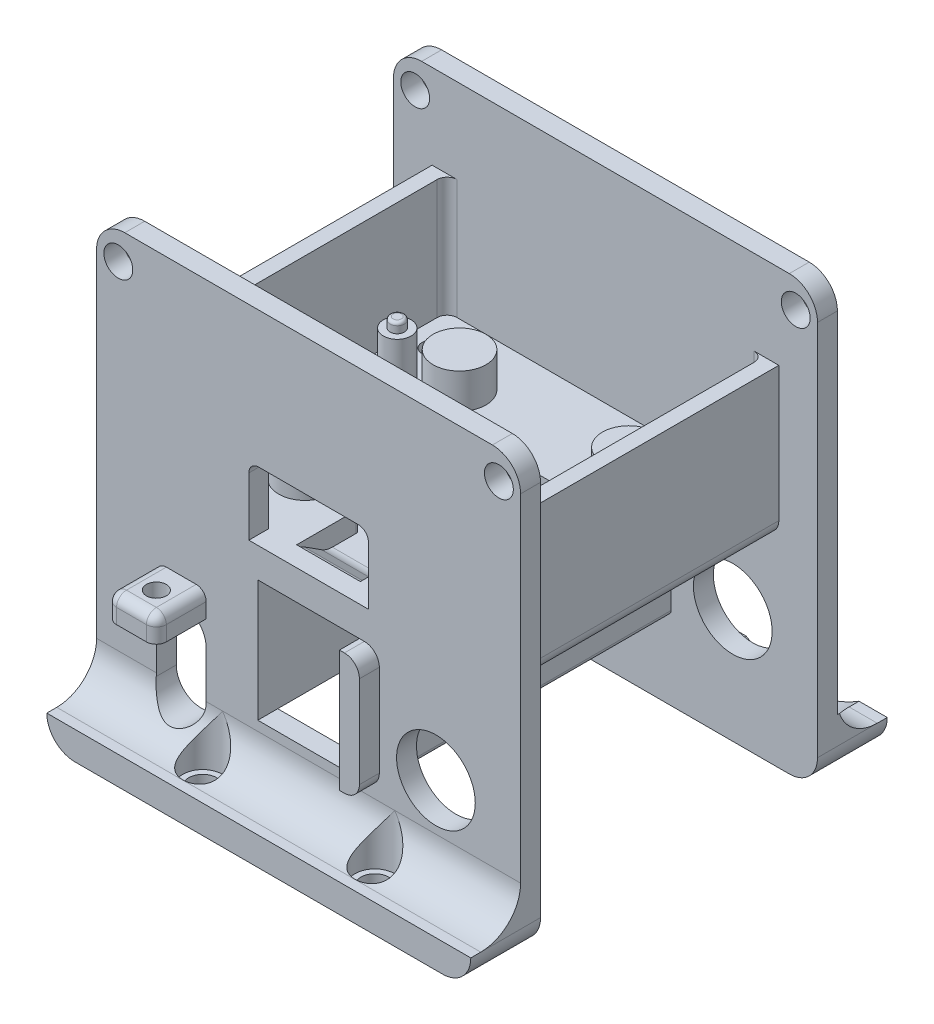
SolidWorks part; units mm, degrees
other "标注1"
sketch "草图55" plane through (-21.28, -20, 20.9) normal (0, 0, 1) x (1, 0, 0)
material "尼龙 101"
ref_plane "前视基准面" through (0, 0, 0) normal (0, 0, 1) x (1, 0, 0)
ref_plane "上视基准面" through (0, 0, 0) normal (0, 1, 0) x (1, 0, 0)
ref_plane "右视基准面" through (0, 0, 0) normal (1, 0, 0) x (0, 0, -1)
other "Configuration Table"
sketch "草图1" plane through (0, 0, 0) normal (0, 1, 0) x (1, 0, 0)
  line L1 (-15.9, 13.9) -> (15.9, 13.9)
  line L2 (-15.9, 13.9) -> (-15.9, -13.9)
  line L3 (-15.9, -13.9) -> (15.9, -13.9)
  line L4 (15.9, 13.9) -> (15.9, -13.9)
  line L5 (-15.9, 13.9) -> (15.9, -13.9) construction
  line L6 (-15.9, -13.9) -> (15.9, 13.9) construction
  point P0 (0, 0)
  dimension "D1" = 31.8
  dimension "D2" = 27.8
extrude "凸台-拉伸1" add sketch "草图1" along normal blind 3
sketch "草图2" plane through (0, 3, 0) normal (0, 1, 0) x (1, 0, 0)
  line L0 (0, 0) -> (0, 5.35) construction
  line L1 (-5.35, 5.35) -> (5.35, 5.35)
  line L2 (5.35, 5.35) -> (5.35, -7.55)
  line L3 (5.35, -7.55) -> (4.35, -7.55)
  line L4 (4.35, -7.55) -> (4.35, 4.35)
  line L5 (4.35, 4.35) -> (-4.35, 4.35)
  line L6 (-4.35, -7.55) -> (-4.35, 4.35)
  line L7 (-5.35, -7.55) -> (-4.35, -7.55)
  line L8 (-5.35, 5.35) -> (-5.35, -7.55)
  point P9 (0, 4.35)
  dimension "D1" = 8.7
  dimension "D2" = 11.9
  dimension "D3" = 4.35
  dimension "D4" = 1
  dimension "D5" = 1
extrude "凸台-拉伸2" add sketch "草图2" along normal blind 1.5
sketch "草图5" plane through (0, 3, 0) normal (0, 1, 0) x (1, 0, 0)
  line L0 (0, 13.9) -> (0, 0) construction
  line L1 (15.9, 13.9) -> (-15.9, 13.9) construction
  line L2 (0, 0) -> (15.9, 0) construction
  line L3 (15.9, -13.9) -> (15.9, 13.9) construction
  circle A0 centre (12.5, 5.5) radius 1.4
  circle A1 centre (12.5, -5.5) radius 1.4
  circle A2 centre (-12.5, -5.5) radius 1.4
  circle A3 centre (-12.5, 5.5) radius 1.4
  dimension "D1" = 2.8
  dimension "D2" = 25
  dimension "D3" = 11
extrude "凸台-拉伸3" add sketch "草图5" along normal blind 4.5
sketch "草图6" plane through (0, 7.5, 0) normal (0, 1, 0) x (1, 0, 0)
  circle A0 centre (-12.5, -5.5) radius 0.725
  circle A1 centre (-12.5, 5.5) radius 0.725
  circle A2 centre (12.5, 5.5) radius 0.725
  circle A3 centre (12.5, -5.5) radius 0.725
  dimension "D1" = 1.45
extrude "凸台-拉伸4" add sketch "草图6" along normal blind 1
sketch "草图7" plane through (0, 3, 0) normal (0, 1, 0) x (1, 0, 0)
  line L0 (0, 0) -> (0, 13.9) construction
  line L1 (15.9, 13.9) -> (-15.9, 13.9) construction
  line L2 (0, 0) -> (15.9, 0) construction
  line L3 (15.9, -13.9) -> (15.9, 13.9) construction
  circle A0 centre (13.5, 10) radius 1
  circle A1 centre (-13.5, 10) radius 1
  circle A2 centre (-13.5, -10) radius 1
  circle A3 centre (13.5, -10) radius 1
  dimension "D1" = 2
  dimension "D2" = 20
  dimension "D3" = 27
extrude "切除-拉伸1" cut sketch "草图7" against normal blind 10
sketch "草图8" plane through (0, 0, 0) normal (0, -1, 0) x (1, 0, 0)
  circle A0 centre (-13.5, 10) radius 2
  circle A1 centre (13.5, 10) radius 2
  circle A2 centre (13.5, -10) radius 2
  circle A3 centre (-13.5, -10) radius 2
  dimension "D1" = 4
extrude "切除-拉伸2" cut sketch "草图8" against normal blind 1
fillet "圆角1" radius 1 4 edges at (-15.9, 1.5, -13.9) (15.9, 1.5, -13.9) (-15.9, 1.5, 13.9) (15.9, 1.5, 13.9)
sketch "草图9" plane through (0, 3, 0) normal (0, 1, 0) x (1, 0, 0)
  line L0 (0, 13.9) -> (0, 0) construction
  line L1 (14.9, 13.9) -> (-14.9, 13.9) construction
  line L2 (0, 0) -> (15.9, 0) construction
  line L3 (15.9, -12.9) -> (15.9, 12.9) construction
  circle A0 centre (8.5, 7.75) radius 2.65
  circle A1 centre (-8.5, 7.75) radius 2.65
  circle A2 centre (-8.5, -7.75) radius 2.65
  circle A3 centre (8.5, -7.75) radius 2.65
  dimension "D1" = 17
  dimension "D2" = 15.5
  dimension "D3" = 5.3
extrude "凸台-拉伸5" add sketch "草图9" along normal blind 3.5
fillet "圆角2" radius 0.3 4 edges at (12.5, 8.5, -4.775) (12.5, 8.5, 6.225) (-12.5, 8.5, 6.225) (-12.5, 8.5, -4.775)
sketch "草图15" plane through (0, 3, 0) normal (0, 1, 0) x (1, 0, 0)
  line L0 (0, 0) -> (0, 13.9) construction
  line L1 (14.9, 13.9) -> (-14.9, 13.9) construction
  line L2 (-4.35, 4.35) -> (4.35, 4.35)
  line L3 (4.35, 4.35) -> (4.35, -7.55)
  line L4 (4.35, -7.55) -> (3.2, -7.55)
  line L5 (3.2, -7.55) -> (3.2, -13.9)
  line L6 (-14.9, -13.9) -> (14.9, -13.9) construction
  line L7 (3.2, -13.9) -> (-3.2, -13.9)
  line L8 (-3.2, -7.55) -> (-3.2, -13.9)
  line L9 (-4.35, -7.55) -> (-3.2, -7.55)
  line L10 (-4.35, 4.35) -> (-4.35, -7.55)
  line L11 (4.35, 4.35) -> (4.35, -7.55) construction
  point P14 (0, -13.9)
  point P17 (0, 4.35)
  dimension "D1" = 6.4
extrude "切除-拉伸8" cut sketch "草图15" against normal blind 2
sketch "草图17" plane through (0, 4.5, 0) normal (0, 1, 0) x (1, 0, 0)
  line L8 (-4.35, -7.55) -> (-4.35, 4.35)
  line L9 (-4.35, 4.35) -> (4.35, 4.35)
  line L10 (4.35, 4.35) -> (4.35, -7.55)
  line L11 (4.35, -7.55) -> (5.35, -7.55)
  line L12 (5.35, -7.55) -> (5.35, 5.35)
  line L13 (5.35, 5.35) -> (-5.35, 5.35)
  line L14 (-5.35, 5.35) -> (-5.35, -7.55)
  line L15 (-5.35, -7.55) -> (-4.35, -7.55)
  line L16 (-4.35, -7.55) -> (-4.35, 4.35)
  line L17 (-4.35, 4.35) -> (4.35, 4.35)
  line L18 (4.35, 4.35) -> (4.35, -7.55)
  line L19 (4.35, -7.55) -> (5.35, -7.55)
  line L20 (5.35, -7.55) -> (5.35, 5.35)
  line L21 (5.35, 5.35) -> (-5.35, 5.35)
  line L22 (-5.35, 5.35) -> (-5.35, -7.55)
  line L23 (-5.35, -7.55) -> (-4.35, -7.55)
  dimension "D1" = 0
extrude "切除-拉伸9" cut sketch "草图17" against normal blind 1.5
sketch "草图18" plane through (3.2, 0, 0) normal (-1, 0, 0) x (0, 0, 1)
  line L0 (13.9, 1) -> (10.9, 1)
  line L2 (13.9, 1) -> (13.9, 3) construction
  line L3 (13.9, 2.6) -> (13.9, 1)
  line L5 (13.9, 3) -> (13.9, 0) construction
  line L6 (13.9, 2.6) -> (13.4, 2.6)
  line L7 (13.4, 2.6) -> (10.9, 1)
  line L8 (13.9, 3) -> (12.9, 3) construction
  dimension "D1" = 3
  dimension "D2" = 0.4
  dimension "D3" = 0.5
extrude "凸台-拉伸6" add sketch "草图18" along normal up to surface (6.4 mm away) up to face at (-3.2, 2, 10.725)
fillet "圆角3" radius 2 1 edges at (0, 1, 10.9)
fillet "圆角5" radius 1 1 edges at (0, 2.6, 13.4)
fillet "圆角6" radius 0.4 2 edges at (3.2, 2, 7.55) (-3.2, 2, 7.55)
sketch "草图21" plane through (0, 0, 0) normal (0, -1, 0) x (1, 0, 0)
  line L0 (-14.9, 13.9) -> (14.9, 13.9) construction
  line L1 (-15.9, -12.9) -> (-15.9, 12.9) construction
  line L2 (14.9, -13.9) -> (-14.9, -13.9) construction
  line L3 (15.9, 12.9) -> (15.9, -12.9) construction
  line L4 (-14.9, 13.9) -> (14.9, 13.9)
  line L5 (-15.9, -12.9) -> (-15.9, 12.9)
  line L6 (14.9, -13.9) -> (-14.9, -13.9)
  line L7 (15.9, 12.9) -> (15.9, -12.9)
  line L9 (-17.4, 15.9) -> (17.4, 15.9)
  line L10 (-17.4, 15.9) -> (-17.4, -15.9)
  line L11 (-17.4, -15.9) -> (17.4, -15.9)
  line L12 (17.4, 15.9) -> (17.4, -15.9)
  arc A0 (15.9, 12.9) -> (14.9, 13.9) centre (14.9, 12.9) ccw construction
  arc A1 (-14.9, 13.9) -> (-15.9, 12.9) centre (-14.9, 12.9) ccw construction
  arc A2 (-15.9, -12.9) -> (-14.9, -13.9) centre (-14.9, -12.9) ccw construction
  arc A3 (14.9, -13.9) -> (15.9, -12.9) centre (14.9, -12.9) ccw construction
  arc A4 (15.9, 12.9) -> (14.9, 13.9) centre (14.9, 12.9) ccw
  arc A5 (-14.9, 13.9) -> (-15.9, 12.9) centre (-14.9, 12.9) ccw
  arc A6 (-15.9, -12.9) -> (-14.9, -13.9) centre (-14.9, -12.9) ccw
  arc A7 (14.9, -13.9) -> (15.9, -12.9) centre (14.9, -12.9) ccw
  dimension "D1" = 1.5
  dimension "D2" = 1.5
  dimension "D3" = 2
  dimension "D4" = 2
extrude "凸台-拉伸7" add sketch "草图21" against normal blind 15
sketch "草图22" plane through (0, 0, 15.9) normal (0, 0, 1) x (1, 0, 0)
  line L2 (-21.28, 0) -> (-21.28, 20.67)
  line L3 (-18.45, 23.5) -> (18.45, 23.5)
  line L4 (21.28, 0) -> (21.28, 20.67)
  line L5 (-21.28, 0) -> (21.28, 23.5) construction
  line L6 (-21.28, 23.5) -> (21.28, 0) construction
  line L7 (0, 0) -> (0, 23.5) construction
  line L10 (-21.28, 0) -> (-21.28, -17.17)
  line L11 (-18.45, -20) -> (18.45, -20)
  line L12 (21.28, 0) -> (21.28, -17.17)
  arc A0 (-21.28, 20.67) -> (-18.45, 23.5) centre (-18.45, 20.67) cw
  arc A1 (18.45, 23.5) -> (21.28, 20.67) centre (18.45, 20.67) cw
  arc A4 (18.45, -20) -> (21.28, -17.17) centre (18.45, -17.17) ccw
  arc A5 (-21.28, -17.17) -> (-18.45, -20) centre (-18.45, -17.17) ccw
  circle A6 centre (-19.1, 20.67) radius 1.45
  circle A7 centre (19.1, 20.67) radius 1.45
  point P4 (0, 11.75)
  point P22 (21.28, -20)
  dimension "D3" = 2.83
  dimension "D4" = 2.83
  dimension "D8" = 2.83
  dimension "D1" = 42.56
  dimension "D2" = 23.5
  dimension "D7" = 20
extrude "凸台-拉伸8" add sketch "草图22" against normal blind 2
sketch "草图24" plane through (0, 0, -15.9) normal (0, 0, -1) x (-1, 0, 0)
  line L5 (-18.45, -20) -> (18.45, -20)
  line L6 (-18.45, -20) -> (18.45, -20)
  line L21 (21.28, -17.17) -> (21.28, 20.67)
  line L22 (18.45, 23.5) -> (-18.45, 23.5)
  line L23 (-21.28, 20.67) -> (-21.28, -17.17)
  line L37 (21.28, -17.17) -> (21.28, 20.67)
  line L38 (18.45, 23.5) -> (-18.45, 23.5)
  line L39 (-21.28, 20.67) -> (-21.28, -17.17)
  arc A2 (21.28, 20.67) -> (18.45, 23.5) centre (18.45, 20.67) ccw
  arc A3 (-18.45, 23.5) -> (-21.28, 20.67) centre (-18.45, 20.67) ccw
  arc A4 (21.28, 20.67) -> (18.45, 23.5) centre (18.45, 20.67) ccw
  arc A5 (-18.45, 23.5) -> (-21.28, 20.67) centre (-18.45, 20.67) ccw
  circle A8 centre (-19.1, 20.67) radius 1.45
  circle A9 centre (19.1, 20.67) radius 1.45
  arc A12 (-21.28, -17.17) -> (-18.45, -20) centre (-18.45, -17.17) ccw
  arc A13 (-21.28, -17.17) -> (-18.45, -20) centre (-18.45, -17.17) ccw
  arc A14 (18.45, -20) -> (21.28, -17.17) centre (18.45, -17.17) ccw
  arc A15 (18.45, -20) -> (21.28, -17.17) centre (18.45, -17.17) ccw
  dimension "D1" = 0
extrude "凸台-拉伸9" add sketch "草图24" against normal blind 2
sketch "草图25" plane through (0, 0, 15.9) normal (0, 0, 1) x (1, 0, 0)
  line L1 (-5, 9.85) -> (5, 9.85)
  line L2 (-6, 8.85) -> (-6, 3)
  line L4 (6, 8.85) -> (6, 3)
  line L5 (-6, 3) -> (6, 3)
  line L9 (-6, 3) -> (6, 9.85) construction
  arc A0 (5, 9.85) -> (6, 8.85) centre (5, 8.85) cw
  arc A1 (-5, 9.85) -> (-6, 8.85) centre (-5, 8.85) ccw
  point P5 (6, 9.85)
  point P8 (0, 6.425)
  point P9 (-6, 9.85)
  dimension "D2" = 1
  dimension "D1" = 12
extrude "切除-拉伸10" cut sketch "草图25" against normal blind 2
sketch "草图27" plane through (0, 0, 15.9) normal (0, 0, 1) x (1, 0, 0)
  line L0 (-5.1, 0) -> (5.1, -12.2) construction
  line L5 (-5.1, 0) -> (5.1, 0) construction
  line L16 (-17.4, 0) -> (17.4, 0) construction
  line L18 (-5.1, 0) -> (-5.1, -12.2)
  line L20 (5.1, 0) -> (5.1, -12.2)
  line L21 (-6.6, 0) -> (-6.6, -11.7)
  line L26 (6.6, 0) -> (6.6, -11.7)
  line L31 (-6.6, 0) -> (-5.1, 0)
  line L33 (-6.1, -12.2) -> (-5.1, -12.2)
  line L34 (-6.6, 1.5) -> (6.6, 1.5) construction
  line L35 (0, 0) -> (0, -4.0507) construction
  line L36 (6.6, 1.5) -> (6.6, -13.7) construction
  line L37 (-6.6, 1.5) -> (-6.6, -13.7) construction
  line L38 (5.1, 0) -> (6.6, 0)
  line L39 (-6.6, -13.7) -> (6.6, -13.7) construction
  line L40 (-5.1, -12.2) -> (5.1, -12.2) construction
  line L41 (5.1, -12.2) -> (6.1, -12.2)
  arc A4 (6.1, -12.2) -> (6.6, -11.7) centre (6.1, -11.7) ccw
  arc A5 (-6.6, -11.7) -> (-6.1, -12.2) centre (-6.1, -11.7) ccw
  point P6 (-2.5, 0)
  point P7 (6.9808, -17.5163)
  point P19 (6.6, -12.2)
  point P24 (0, -6.1)
  dimension "D4" = 0.5
  dimension "D1" = 10.2
  dimension "D2" = 12.2
  dimension "D3" = 1.5
extrude "凸台-拉伸10" add sketch "草图27" against normal up to surface (29.8 mm away) up to face at (0, 8.25, -13.9)
sketch "草图35" plane through (0, 0, 15.9) normal (0, 0, 1) x (1, 0, 0)
  line L1 (-5.1, 0) -> (5.1, 0)
  line L2 (-5.1, 0) -> (-5.1, -12.2)
  line L3 (-5.1, -12.2) -> (5.1, -12.2)
  line L4 (5.1, 0) -> (5.1, -12.2)
extrude "切除-拉伸14" cut sketch "草图35" against normal through all
sketch "草图43" plane through (0, 0, 15.9) normal (0, 0, 1) x (1, 0, 0)
  line L0 (-21.28, -17.17) -> (21.28, -17.17)
  line L1 (-18.45, -20) -> (18.45, -20) construction
  line L2 (-18.45, -20) -> (18.45, -20)
  arc A1 (18.45, -20) -> (21.28, -17.17) centre (18.45, -17.17) ccw construction
  arc A3 (-21.28, -17.17) -> (-18.45, -20) centre (-18.45, -17.17) ccw construction
  arc A4 (18.45, -20) -> (21.28, -17.17) centre (18.45, -17.17) ccw
  arc A5 (-21.28, -17.17) -> (-18.45, -20) centre (-18.45, -17.17) ccw
extrude "凸台-拉伸14" add sketch "草图43" along normal blind 5
sketch "草图44" plane through (-21.28, 0, 0) normal (-1, 0, 0) x (0, 0, 1)
  line L3 (15.9, -13.17) -> (15.9, -17.17)
  line L4 (15.9, -17.17) -> (19.9, -17.17)
  arc A0 (19.9, -17.17) -> (15.9, -13.17) centre (19.9, -13.17) cw
  point P8 (15.9, -17.17)
  dimension "D1" = 4
extrude "凸台-拉伸15" add sketch "草图44" against normal up to surface (42.56 mm away) up to face at (21.28, 1.75, 14.9)
sketch "草图45" plane through (0, 0, -15.9) normal (0, 0, -1) x (-1, 0, 0)
  line L0 (-18.45, -20) -> (18.45, -20) construction
  line L1 (-21.28, -17.17) -> (21.28, -17.17) construction
  line L2 (-18.45, -20) -> (18.45, -20)
  line L3 (-21.28, -17.17) -> (21.28, -17.17)
  arc A0 (-21.28, -17.17) -> (-18.45, -20) centre (-18.45, -17.17) ccw construction
  arc A1 (18.45, -20) -> (21.28, -17.17) centre (18.45, -17.17) ccw construction
  arc A2 (-21.28, -17.17) -> (-18.45, -20) centre (-18.45, -17.17) ccw
  arc A3 (18.45, -20) -> (21.28, -17.17) centre (18.45, -17.17) ccw
extrude "凸台-拉伸16" add sketch "草图45" along normal blind 5
sketch "草图46" plane through (21.28, 0, 0) normal (1, 0, 0) x (0, 0, -1)
  line L0 (15.9, -13.17) -> (15.9, -17.17)
  line L1 (15.9, -17.17) -> (19.9, -17.17)
  arc A0 (15.9, -13.17) -> (19.9, -17.17) centre (19.9, -13.17) ccw
  point P7 (15.9, -17.17)
  dimension "D1" = 4
extrude "凸台-拉伸17" add sketch "草图46" against normal up to surface (42.56 mm away) up to face at (-21.28, 1.75, -14.9)
sketch "草图36" plane through (0, 0, 15.9) normal (0, 0, 1) x (1, 0, 0)
  line L0 (-5.1, 0) -> (5.1, -12.2) construction
  line L1 (5.1, 0) -> (-5.1, -12.2) construction
  line L2 (-5.1, -12.2) -> (5.1, -12.2) construction
  line L3 (-5.1, 0) -> (-5.1, -12.2) construction
  line L6 (-5.1, -12.2) -> (-5.1, -13.2) construction
  line L7 (-5.1, -13.2) -> (22.8364, -13.2) construction
  line L8 (21.28, -13.17) -> (21.28, 20.67) construction
  line L10 (-15.28, -8.4815) -> (-15.28, -13.4815)
  line L12 (-10.28, -13.4815) -> (-10.28, -8.4815)
  circle A0 centre (0, -6.1) radius 4.5 construction
  circle A3 centre (12.78, -8.4815) radius 8.5 construction
  circle A6 centre (12.78, -8.4815) radius 5.75 construction
  circle A7 centre (12.78, -8.4815) radius 3.95
  arc A9 (-10.28, -8.4815) -> (-15.28, -8.4815) centre (-12.78, -8.4815) ccw
  arc A11 (-15.28, -13.4815) -> (-10.28, -13.4815) centre (-12.78, -13.4815) ccw
  point P11 (0, -6.1)
  dimension "D1" = 9
  dimension "D2" = 17
  dimension "D3" = 7.9
  dimension "D4" = 9
  dimension "D5" = 11.5
extrude "切除-拉伸15" cut sketch "草图36" against normal through all both and the other way through all
sketch "草图37" plane through (0, 0, 15.9) normal (0, 0, 1) x (1, 0, 0)
  line L0 (-15.28, -5.9815) -> (-15.28, -3.4815)
  line L1 (-15.28, -3.4815) -> (-10.28, -3.4815)
  line L2 (-10.28, -3.4815) -> (-10.28, -5.9815)
  line L3 (-15.28, -5.9815) -> (-10.28, -5.9815)
extrude "凸台-拉伸11" add sketch "草图37" along normal blind 5
sketch "草图38" plane through (0, 0, -15.9) normal (0, 0, -1) x (-1, 0, 0)
  line L0 (15.28, -3.4815) -> (15.28, -5.9815) construction
  line L1 (10.28, -5.9815) -> (10.28, -3.4815) construction
  line L2 (10.28, -3.4815) -> (15.28, -3.4815) construction
  line L3 (15.28, -3.4815) -> (15.28, -5.9815)
  line L4 (10.28, -5.9815) -> (10.28, -3.4815)
  line L5 (10.28, -3.4815) -> (15.28, -3.4815)
  line L6 (10.28, -5.9815) -> (15.28, -5.9815)
extrude "凸台-拉伸12" add sketch "草图38" along normal blind 5
fillet "圆角7" radius 1 2 edges at (-10.28, -4.7315, 20.9) (-15.28, -4.7315, 20.9)
fillet "圆角8" radius 1 2 edges at (-10.28, -4.7315, -20.9) (-15.28, -4.7315, -20.9)
sketch "草图41" plane through (0, 0, 15.9) normal (0, 0, 1) x (1, 0, 0)
  line L1 (5.1, 0) -> (5.6, 0)
  line L2 (5.1, 0) -> (5.1, -12.2)
  line L3 (5.1, -12.2) -> (5.6, -12.2)
  line L4 (7.1, -1.5) -> (7.1, -10.7)
  arc A0 (5.6, -12.2) -> (7.1, -10.7) centre (5.6, -10.7) ccw
  arc A1 (7.1, -1.5) -> (5.6, 0) centre (5.6, -1.5) ccw
  dimension "D1" = 1.5
  dimension "D2" = 2
extrude "凸台-拉伸13" add sketch "草图41" along normal blind 2
sketch "草图42" plane through (0, -3.4815, 0) normal (0, 1, 0) x (1, 0, 0)
  line L0 (-14.9871, 20.6071) -> (-10.28, 15.9) construction
  line L1 (-15.28, -15.9) -> (-10.5729, -20.6071) construction
  line L2 (-10.5729, 20.6071) -> (-15.28, 15.9) construction
  line L3 (-10.28, -15.9) -> (-14.9871, -20.6071) construction
  arc A0 (-14.28, 20.9) -> (-15.28, 19.9) centre (-14.28, 19.9) ccw construction
  arc A1 (-10.28, 19.9) -> (-11.28, 20.9) centre (-11.28, 19.9) ccw construction
  arc A2 (-11.28, -20.9) -> (-10.28, -19.9) centre (-11.28, -19.9) ccw construction
  arc A3 (-15.28, -19.9) -> (-14.28, -20.9) centre (-14.28, -19.9) ccw construction
  circle A4 centre (-12.78, -18.4) radius 1
  circle A5 centre (-12.78, 18.4) radius 1
  point P24 (-12.78, 18.4)
  point P25 (-12.78, -18.4)
  dimension "D1" = 2
  dimension "D2" = 2
sketch "草图49" plane through (0, -20, 0) normal (0, -1, 0) x (1, 0, 0)
  line L5 (8.64, 17.89) -> (-8.64, -17.89) construction
  line L6 (-8.64, 17.89) -> (8.64, 17.89) construction
  line L7 (-8.64, 17.89) -> (-8.64, -17.89) construction
  line L8 (-8.64, -17.89) -> (8.64, -17.89) construction
  line L9 (8.64, 17.89) -> (8.64, -17.89) construction
  circle A1 centre (-8.64, 17.89) radius 1.4
  circle A2 centre (8.64, 17.89) radius 1.4
  circle A3 centre (8.64, -17.89) radius 1.4
  circle A4 centre (-8.64, -17.89) radius 1.4
  point P6 (0, 0)
  dimension "D1" = 17.28
  dimension "D2" = 35.78
extrude "切除-拉伸17" cut sketch "草图49" against normal blind 6
sketch "草图51" plane through (0, 0, -15.9) normal (0, 0, -1) x (-1, 0, 0)
  circle A3 centre (-12.78, -8.4815) radius 10.3764
extrude "切除-拉伸18" cut sketch "草图51" along normal blind 6
sketch "草图52" plane through (0, -17.17, 0) normal (0, 1, 0) x (1, 0, 0)
  circle A3 centre (-8.64, -17.89) radius 1.99
  circle A4 centre (-8.64, 17.89) radius 1.99
  circle A5 centre (8.64, 17.89) radius 1.99
  circle A6 centre (8.64, -17.89) radius 1.99
extrude "切除-拉伸19" cut sketch "草图52" against normal blind 1.5
extrude "切除-拉伸20" cut sketch "草图52<2>" along normal blind 4
sketch "草图52<2>" plane through (0, -17.17, 0) normal (0, 1, 0) x (1, 0, 0) same geometry as "草图52"
fillet "圆角10" radius 1 5 edges at (-14.9871, -3.4815, 20.6071) (-12.78, -3.4815, 20.9) (-10.5729, -3.4815, 20.6071) (-10.28, -3.4815, 17.9) (-15.28, -3.4815, 17.9)
fillet "圆角12" radius 1 5 edges at (-15.28, -3.4815, -17.9) (-14.9871, -3.4815, -20.6071) (-12.78, -3.4815, -20.9) (-10.5729, -3.4815, -20.6071) (-10.28, -3.4815, -17.9)
extrude "切除-拉伸21" cut sketch "草图42" against normal blind 4
ref_plane "基准面7" through (0, 0, -6.3) normal (0, 0, -1) x (-1, 0, 0)
sketch "草图54" plane through (0, 0, -6.3) normal (0, 0, -1) x (-1, 0, 0)
  line L0 (-5.1, 0) -> (5.1, -12.2) construction
  line L1 (-5.1, 0) -> (5.1, 0)
  line L2 (-5.1, 0) -> (-5.1, -12.2)
  line L3 (-5.1, -12.2) -> (5.1, -12.2)
  line L4 (5.1, 0) -> (5.1, -12.2)
  line L5 (0, -1.6) -> (0, -10.6) construction
  circle A0 centre (0, -1.6) radius 0.8
  circle A1 centre (0, -10.6) radius 0.8
  circle A2 centre (0, -6.1) radius 1.8
  point P8 (0, -6.1)
  point P11 (0, -6.1)
  dimension "D1" = 9
  dimension "D2" = 0
  dimension "D3" = 0
extrude "凸台-拉伸18" add sketch "草图54" along normal blind 2
fillet "圆角13" radius 1.5 2 edges at (17.4, 0, 0) (-17.4, 0, 0)
fillet "圆角14" radius 0.8 4 edges at (0, -12.2, -15.9) (-5.1, -6.1, -15.9) (0, 0, -15.9) (5.1, -6.1, -15.9)
